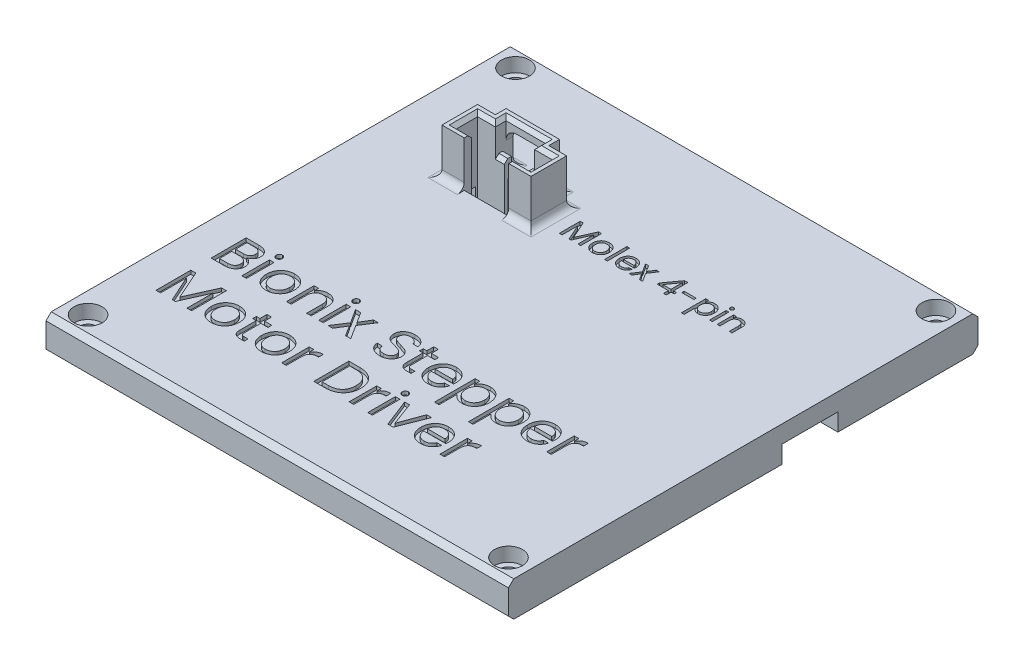
SolidWorks part; units mm, degrees
ref_plane "Front Plane" through (0, 0, 0) normal (0, 0, 1) x (1, 0, 0)
ref_plane "Top Plane" through (0, 0, 0) normal (0, 1, 0) x (1, 0, 0)
ref_plane "Right Plane" through (0, 0, 0) normal (1, 0, 0) x (0, 0, -1)
sketch "Sketch1" plane through (0, 0, 0) normal (0, 1, 0) x (1, 0, 0)
  line L1 (0, 0) -> (66, 0)
  line L2 (0, 0) -> (0, 67)
  line L3 (0, 67) -> (66, 67)
  line L4 (66, 0) -> (66, 67)
  dimension "D1" = 67
  dimension "D2" = 66
extrude "Boss-Extrude1" add sketch "Sketch1" along normal blind 5
chamfer "Chamfer1" distance 0.75 angle 45 4 edges at (33, 5, 0) (33, 5, -67) (33, 0, -67) (33, 0, 0)
sketch "Sketch2" plane through (0, 0, 0) normal (0, -1, 0) x (1, 0, 0)
  line L0 (0, -66.25) -> (0, -0.75) construction
  line L1 (7.3, -49) -> (28, -49)
  line L2 (7.3, -49) -> (7.3, -39)
  line L3 (7.3, -39) -> (27.8, -39)
  line L4 (28, -49) -> (28, -47)
  line L5 (0, -67) -> (66, -67) construction
  line L6 (66, -0.75) -> (66, -66.25) construction
  line L7 (28, -47) -> (66, -47)
  line L9 (27.8, -39) -> (66, -39)
  line L10 (66, -47) -> (66, -39)
  dimension "D1" = 7.3
  dimension "D2" = 18
  dimension "D3" = 20.5
  dimension "D4" = 20
  dimension "D5" = 28
  dimension "D6" = 28
extrude "Cut-Extrude1" cut sketch "Sketch2" against normal blind 2.5 contours L7 L10 L9 L3 L2 L1 L4
sketch "Sketch3" plane through (0, 5, 0) normal (0, 1, 0) x (1, 0, 0)
  line L0 (0, 64) -> (66, 64) construction
  line L1 (0, 66.25) -> (0, 0.75) construction
  line L2 (66, 0.75) -> (66, 66.25) construction
  line L3 (0, 3) -> (66, 3) construction
  line L4 (0, 67) -> (66, 67) construction
  line L6 (66, 0) -> (0, 0) construction
  circle A0 centre (3, 64) radius 2
  circle A1 centre (63, 64) radius 2
  circle A2 centre (63, 3) radius 2
  circle A3 centre (3, 3) radius 2
  dimension "D3" = 4
  dimension "D4" = 4
  dimension "D5" = 4
  dimension "D6" = 4
  dimension "D7" = 3
  dimension "D8" = 3
  dimension "D1" = 3
  dimension "D2" = 3
extrude "Cut-Extrude2" cut sketch "Sketch3" against normal blind 2
sketch "Sketch4" plane through (0, 2.5, 0) normal (0, -1, 0) x (1, 0, 0)
  point P6 (17.65, -47.75)
  point P19 (17.65, -47.75)
sketch "Sketch5" plane through (0, 3, 0) normal (0, 1, 0) x (1, 0, 0)
  circle A0 centre (3, 64) radius 1.2
  circle A1 centre (3, 3) radius 1.2
  circle A2 centre (63, 3) radius 1.2
  circle A3 centre (63, 64) radius 1.2
  dimension "D1" = 2.4
  dimension "D2" = 2.4
  dimension "D3" = 2.4
  dimension "D4" = 2.4
extrude "Cut-Extrude3" cut sketch "Sketch5" against normal up to surface (3 mm away) up to face at (33.46, 0, -40.4)
sketch "Sketch7" plane through (0, 5, 0) normal (0, 1, 0) x (1, 0, 0)
  text T0 "Bionix Stepper " font "Poppins" height 5
  text T1 "Motor Driver" font "Poppins" height 5
extrude "Cut-Extrude6" cut sketch "Sketch7" against normal blind 0.5
sketch "Sketch8" plane through (0, 5, 0) normal (0, 1, 0) x (1, 0, 0)
  line L1 (12.316, 46.226) -> (14.475, 46.226)
  line L2 (12.316, 46.226) -> (12.316, 49.274)
  line L3 (12.316, 49.274) -> (16.126, 49.274)
  line L4 (22.984, 46.226) -> (22.984, 49.274)
  line L5 (14.475, 45.21) -> (15.745, 45.21)
  line L6 (14.475, 45.21) -> (14.475, 46.226)
  line L10 (19.555, 45.21) -> (20.825, 45.21)
  line L13 (20.825, 45.21) -> (20.825, 46.226)
  line L15 (16.126, 49.274) -> (16.126, 49.782)
  line L16 (16.126, 49.782) -> (19.174, 49.782)
  line L17 (19.174, 49.274) -> (19.174, 49.782)
  line L19 (19.174, 49.274) -> (22.984, 49.274)
  line L21 (20.825, 46.226) -> (22.984, 46.226)
  line L22 (15.745, 45.21) -> (19.555, 45.21)
  line L25 (66, 0.75) -> (66, 66.25) construction
  line L26 (66, 66.25) -> (0, 66.25) construction
  dimension "D1" = 43.016
  dimension "D2" = 45.175
  dimension "D3" = 46.445
  dimension "D4" = 46.826
  dimension "D5" = 16.468
  dimension "D6" = 16.976
  dimension "D7" = 21.04
extrude "Cut-Extrude7" cut sketch "Sketch8" against normal blind 10
sketch "Sketch10" plane through (0, 5, 0) normal (0, 1, 0) x (1, 0, 0)
  line L1 (14.475, 45.21) -> (12.316, 45.21)
  line L2 (14.475, 45.21) -> (14.475, 46.226)
  line L3 (14.475, 46.226) -> (12.316, 46.226)
  line L5 (11.3, 45.21) -> (12.316, 45.21)
  line L6 (11.3, 45.21) -> (11.3, 50.29)
  line L7 (11.3, 50.29) -> (12.316, 50.29)
  line L8 (12.316, 46.226) -> (12.316, 49.274)
  line L10 (20.825, 45.21) -> (22.984, 45.21)
  line L11 (20.825, 45.21) -> (20.825, 46.226)
  line L12 (20.825, 46.226) -> (22.984, 46.226)
  line L14 (22.984, 45.21) -> (24, 45.21)
  line L15 (22.984, 46.226) -> (22.984, 49.274)
  line L16 (22.984, 50.29) -> (24, 50.29)
  line L17 (24, 45.21) -> (24, 50.29)
  line L20 (22.984, 49.274) -> (19.174, 49.274)
  line L22 (22.984, 50.29) -> (21.46, 50.29)
  line L23 (19.174, 49.274) -> (19.174, 50.29)
  line L24 (14.856, 50.29) -> (16.126, 50.29)
  line L26 (20.444, 50.29) -> (20.444, 51.814)
  line L27 (20.444, 51.814) -> (21.46, 51.814)
  line L28 (21.46, 50.29) -> (21.46, 51.814)
  line L29 (12.316, 49.274) -> (16.126, 49.274)
  line L31 (12.316, 50.29) -> (13.84, 50.29)
  line L32 (16.126, 49.274) -> (16.126, 50.29)
  line L34 (14.856, 50.29) -> (14.856, 51.814)
  line L35 (14.856, 51.814) -> (13.84, 51.814)
  line L36 (13.84, 50.29) -> (13.84, 51.814)
  line L37 (20.444, 50.29) -> (19.174, 50.29)
  line L38 (66, 0.75) -> (66, 66.25) construction
  dimension "D1" = 44.54
  dimension "D2" = 46.826
extrude "Boss-Extrude2" add sketch "Sketch10" along normal blind 6.5
sketch "Sketch11" plane through (0, 11.5, 0) normal (0, 1, 0) x (1, 0, 0)
  line L0 (20.444, 51.814) -> (20.444, 50.29) construction
  line L1 (14.856, 51.814) -> (20.444, 51.814)
  line L3 (14.856, 50.798) -> (20.444, 50.798)
  line L4 (20.444, 51.814) -> (20.444, 50.798)
  line L6 (14.856, 51.814) -> (14.856, 50.798)
  line L9 (12.316, 49.274) -> (16.126, 49.274) construction
  dimension "D1" = 1.524
extrude "Boss-Extrude3" add sketch "Sketch11" against normal blind 1.4
sketch "Sketch12" plane through (0, 11.5, 0) normal (0, 1, 0) x (1, 0, 0)
  line L1 (16.126, 49.274) -> (14.856, 49.274)
  line L2 (16.126, 49.274) -> (16.126, 50.29)
  line L3 (16.126, 50.29) -> (14.856, 50.29)
  line L4 (14.856, 49.274) -> (14.856, 50.29)
  line L5 (19.174, 49.274) -> (20.444, 49.274)
  line L6 (19.174, 49.274) -> (19.174, 50.29)
  line L7 (19.174, 50.29) -> (20.444, 50.29)
  line L8 (20.444, 49.274) -> (20.444, 50.29)
extrude "Cut-Extrude8" cut sketch "Sketch12" against normal blind 4
sketch "Sketch6" plane through (0, 5, 0) normal (0, 1, 0) x (1, 0, 0)
  text T0 "Molex 4-pin\r\n" font "Poppins" height 3
extrude "Cut-Extrude4" cut sketch "Sketch6" against normal blind 0.5
fillet "Fillet1" radius 1.5 2 edges at (20.444, 10.1, -51.306) (14.856, 10.1, -51.306)
chamfer "Chamfer2" distance 0.5 angle 45 9 edges at (21.9045, 11.5, -46.226) (22.984, 11.5, -47.75) (21.714, 11.5, -49.274) (20.444, 11.5, -50.036) (13.3955, 11.5, -46.226) (17.65, 11.5, -50.798) (14.856, 11.5, -50.036) (13.586, 11.5, -49.274) (12.316, 11.5, -47.75)
chamfer "Chamfer3" distance 0.5 angle 45 2 edges at (19.809, 7.5, -49.274) (15.491, 7.5, -49.274)
fillet "Fillet2" radius 1 14 edges at (13.84, 5, -51.052) (14.348, 5, -51.814) (12.57, 5, -50.29) (20.952, 5, -51.814) (21.46, 5, -51.052) (22.73, 5, -50.29) (24, 5, -47.75) (22.4125, 5, -45.21) (11.3, 5, -47.75) (12.8875, 5, -45.21) (15.491, 5, -50.29) (14.856, 5, -51.052) (19.809, 5, -50.29) (20.444, 5, -51.052)
